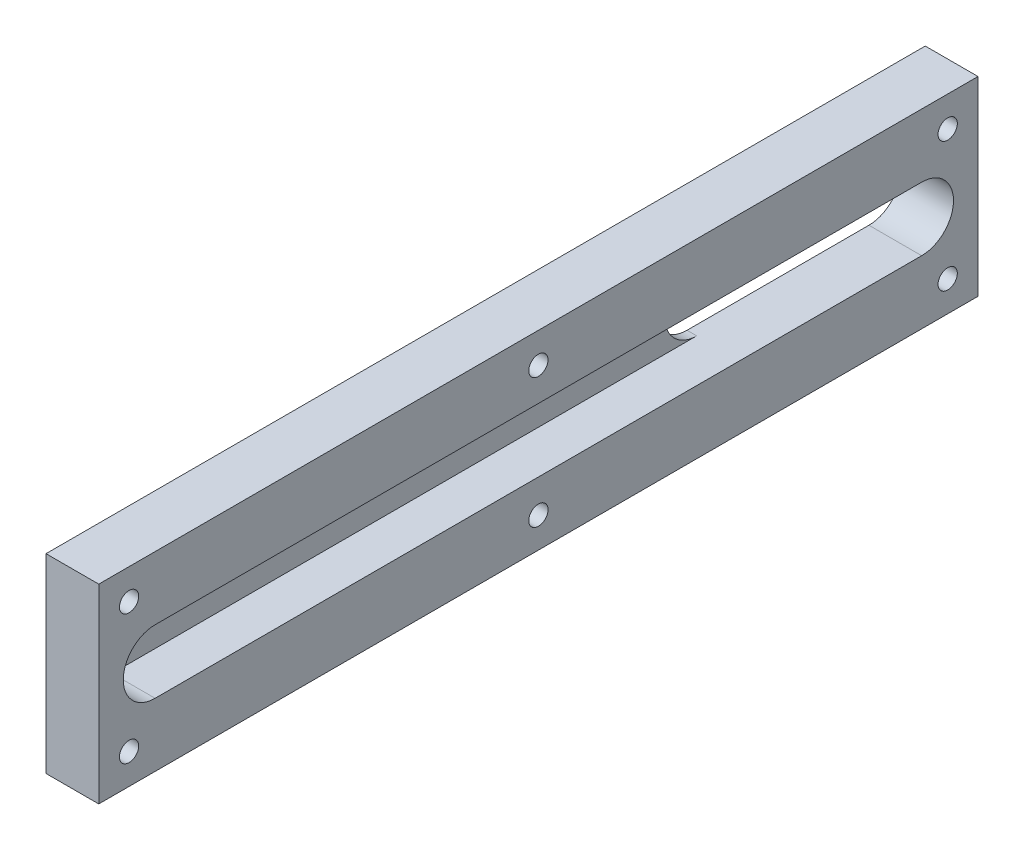
SolidWorks part; units mm, degrees
material "Delrin 2700 NC010, Low Viscosity Acetal Copolymer (SS)"
ref_plane "Front" through (0, 0, 0) normal (0, 0, 1) x (1, 0, 0)
ref_plane "Top" through (0, 0, 0) normal (0, 1, 0) x (1, 0, 0)
ref_plane "Right" through (0, 0, 0) normal (1, 0, 0) x (0, 0, -1)
sketch "Sketch1" plane through (0, 0, 0) normal (1, 0, 0) x (0, 0, -1)
  line L0 (-80.2752, 0) -> (80.2752, 0) construction
  line L1 (92.075, -19.939) -> (-92.075, -19.939)
  line L2 (92.075, -19.939) -> (92.075, 19.939)
  line L3 (92.075, 19.939) -> (-92.075, 19.939)
  line L4 (-92.075, -19.939) -> (-92.075, 19.939)
  line L5 (92.075, -19.939) -> (-92.075, 19.939) construction
  line L6 (92.075, 19.939) -> (-92.075, -19.939) construction
  line L7 (-80.2752, 6.6675) -> (80.2752, 6.6675)
  line L8 (-80.2752, -6.6675) -> (80.2752, -6.6675)
  arc A0 (-80.2752, 6.6675) -> (-80.2752, -6.6675) centre (-80.2752, 0) ccw
  arc A1 (80.2752, -6.6675) -> (80.2752, 6.6675) centre (80.2752, 0) ccw
  point P0 (0, 0)
  point P8 (0, 0)
  dimension "D4" = 13.335
  dimension "D1" = 160.5505
  dimension "D2" = 184.15
  dimension "D3" = 39.878
extrude "Boss-Extrude1" add sketch "Sketch1" along normal blind 11.049
hole_wizard "#10-32 Tapped Hole1" positions "Sketch3" profile "Sketch4" tap size "#10-32" standard "ANSI Inch" end condition through all
sketch "Sketch3" plane through (11.049, 0, 0) normal (1, 0, 0) x (0, 0, -1)
  line L0 (-85.725, 13.589) -> (0, 13.589) construction
  line L1 (0, 13.589) -> (85.725, 13.589) construction
  line L3 (-85.725, 19.939) -> (-85.725, 13.589) construction
  line L4 (92.075, 19.939) -> (-92.075, 19.939) construction
  line L5 (-85.725, 13.589) -> (-85.725, -13.589) construction
  line L6 (-85.725, -13.589) -> (-85.725, -19.939) construction
  line L7 (-92.075, -19.939) -> (92.075, -19.939) construction
  line L8 (-92.075, 19.939) -> (-92.075, -19.939) construction
  point P0 (-85.725, 13.589)
  point P2 (-85.725, -13.589)
  point P4 (0, -13.589)
  point P6 (85.725, -13.589)
  point P8 (85.725, 13.589)
  point P10 (0, 13.589)
  dimension "D1" = 6.35
  dimension "D2" = 6.35
sketch "Sketch4" plane through (11.049, 13.589, 85.725) normal (0, 1, 0) x (0, 0, -1)
  line L0 (0, 0) -> (0, 11.049)
  line L1 (0, 11.049) -> (2.0193, 11.049)
  line L2 (2.0193, 11.049) -> (2.0193, 0)
  line L5 (2.0193, 0) -> (0, 0)
  line L11 (0, -6.35) -> (0, 107.95) construction
  dimension "Thru Tap Drill Dia." = 4.0386
  dimension "Thru Tap Drill Depth" = 11.049
cosmetic thread "Hole Thread1" parameters "D2"=4.826
cosmetic thread "Hole Thread2" parameters "D2"=4.826
cosmetic thread "Hole Thread3" parameters "D2"=4.826
cosmetic thread "Hole Thread4" parameters "D2"=4.826
cosmetic thread "Hole Thread5" parameters "D2"=4.826
cosmetic thread "Hole Thread6" parameters "D2"=4.826
sketch "Sketch5" plane through (0, 0, 0) normal (-1, 0, 0) x (0, 0, 1)
  line L6 (-80.2752, -6.6675) -> (80.2752, -6.6675)
  line L7 (80.2752, 6.6675) -> (-80.2752, 6.6675)
  line L8 (-42.1752, -6.6675) -> (80.2752, -6.6675)
  line L9 (80.2752, 6.6675) -> (-42.1752, 6.6675)
  arc A2 (-42.1752, 6.6675) -> (-42.1752, -6.6675) centre (-42.1752, 0) cw
  arc A6 (-80.2752, 6.6675) -> (-80.2752, -6.6675) centre (-80.2752, 0) ccw construction
  arc A7 (80.2752, -6.6675) -> (80.2752, 6.6675) centre (80.2752, 0) ccw
  arc A8 (-80.2752, 6.6675) -> (-80.2752, -6.6675) centre (-80.2752, 0) ccw
  arc A9 (80.2752, -6.6675) -> (80.2752, 6.6675) centre (80.2752, 0) ccw
  dimension "D2" = 38.1
  dimension "D1" = 0
extrude "Boss-Extrude2" add sketch "Sketch5" against normal blind 2.032
